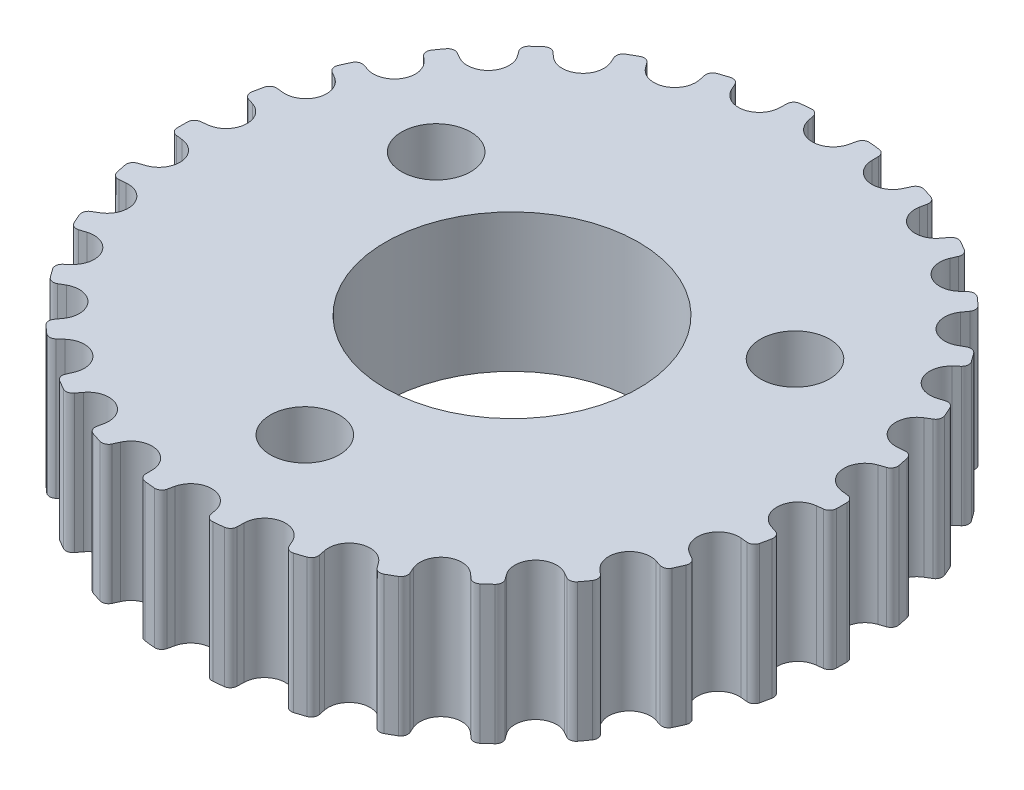
SolidWorks part; units mm, degrees
material "Acrylic (Medium-high impact)"
ref_plane "Front Plane" through (0, 0, 0) normal (0, 0, 1) x (1, 0, 0)
ref_plane "Top Plane" through (0, 0, 0) normal (0, 1, 0) x (1, 0, 0)
ref_plane "Right Plane" through (0, 0, 0) normal (1, 0, 0) x (0, 0, -1)
sketch "Sketch1" plane through (0, 0, 0) normal (0, 1, 0) x (1, 0, 0)
  circle A0 centre (0, 0) radius 14.3239
  dimension "D1" = 28.6479
extrude "Boss-Extrude1" add sketch "Sketch1" along normal blind 6
sketch "Sketch2" plane through (0, 6, 0) normal (0, 1, 0) x (1, 0, 0)
  line L0 (0, 0) -> (0, 14.3239) construction
  line L1 (-0.8883, 13.7564) -> (-0.95, 14.0339)
  line L2 (-2.9781, 14.0109) -> (-2.9781, 14.3239)
  line L3 (-2.9781, 14.3239) -> (2.9781, 14.3239)
  line L4 (0.8883, 13.7564) -> (0.95, 14.0339)
  line L5 (2.9781, 14.0109) -> (2.9781, 14.3239)
  circle A0 centre (0, 0) radius 14.3239 construction
  arc A1 (0.8883, 13.7564) -> (-0.8883, 13.7564) centre (0, 13.9539) cw
  arc A2 (-0.95, 14.0339) -> (-1.2694, 14.2676) centre (-1.2428, 13.9688) ccw
  arc A4 (0.95, 14.0339) -> (1.2694, 14.2676) centre (1.2428, 13.9688) cw
  arc A5 (-1.2694, 14.2676) -> (-2.9781, 14.0109) centre (0, 0) ccw
  arc A6 (1.2694, 14.2676) -> (2.9781, 14.0109) centre (0, 0) cw
  circle A8 centre (0, 0) radius 14.3239 construction
  point P11 (0, 14.3239)
  point P19 (0, 13.0439)
  dimension "D3" = 0.3
  dimension "D5" = 0.91
  dimension "D2" = 0.95
  dimension "D4" = 1.28
  dimension "D6" = 12
extrude "Cut-Extrude1" cut sketch "Sketch2" against normal through all
pattern_circular "CirPattern1" count 30 over 360 about axis through (0, 6, 0) along (0, -1, 0) of "Cut-Extrude1"
sketch "Sketch3" plane through (0, 0, 0) normal (0, -1, 0) x (1, 0, 0)
  circle A0 centre (0, 0) radius 5.5
  dimension "D1" = 11
extrude "Cut-Extrude2" cut sketch "Sketch3" against normal through all
sketch "Sketch4" plane through (0, 0, 0) normal (0, -1, 0) x (1, 0, 0)
  line L0 (0, 0) -> (0, 9) construction
  circle A0 centre (0, 9) radius 1.5
  circle A1 centre (7.7942, -4.5) radius 1.5
  circle A2 centre (-7.7942, -4.5) radius 1.5
  point P14 (0, 0)
  dimension "D1" = 3
  dimension "D2" = 9
  dimension "D3" = 3
extrude "Cut-Extrude3" cut sketch "Sketch4" against normal through all
sketch "Sketch5" plane through (0, 0, 0) normal (0, -1, 0) x (1, 0, 0)
  line L60 (8.7383, -10.682) -> (8.9513, -10.8702)
  line L61 (8.7383, -10.682) -> (8.9513, -10.8702)
  line L62 (9.875, -10.0385) -> (9.7101, -9.807)
  line L63 (9.875, -10.0385) -> (9.7101, -9.807)
  line L64 (12.5987, 6.2896) -> (12.3276, 6.2043)
  line L65 (12.5987, 6.2896) -> (12.3276, 6.2043)
  line L66 (11.5369, 7.5738) -> (11.7463, 7.766)
  line L67 (11.5369, 7.5738) -> (11.7463, 7.766)
  line L68 (-3.638, 13.3126) -> (-3.7561, 13.5712)
  line L69 (-3.638, 13.3126) -> (-3.7561, 13.5712)
  line L70 (-4.9382, 13.1871) -> (-4.8817, 12.9085)
  line L71 (-4.9382, 13.1871) -> (-4.8817, 12.9085)
  line L72 (-11.7463, 7.766) -> (-11.5369, 7.5738)
  line L73 (-11.7463, 7.766) -> (-11.5369, 7.5738)
  line L74 (-12.3276, 6.2043) -> (-12.5987, 6.2896)
  line L75 (-12.3276, 6.2043) -> (-12.5987, 6.2896)
  line L76 (-13.1043, 5.1541) -> (-12.8594, 5.0097)
  line L77 (-13.1043, 5.1541) -> (-12.8594, 5.0097)
  line L78 (-13.3481, 3.5057) -> (-13.6311, 3.5327)
  line L79 (-13.3481, 3.5057) -> (-13.6311, 3.5327)
  line L80 (-13.8895, 2.3169) -> (-13.62, 2.2266)
  line L81 (-13.8895, 2.3169) -> (-13.62, 2.2266)
  line L82 (-13.7853, 0.6538) -> (-14.0677, 0.6215)
  line L83 (-13.7853, 0.6538) -> (-14.0677, 0.6215)
  line L84 (-14.0677, -0.6215) -> (-13.7853, -0.6538)
  line L85 (-14.0677, -0.6215) -> (-13.7853, -0.6538)
  line L86 (-13.62, -2.2266) -> (-13.8895, -2.3169)
  line L87 (-13.62, -2.2266) -> (-13.8895, -2.3169)
  line L88 (-13.6311, -3.5327) -> (-13.3481, -3.5057)
  line L89 (-13.6311, -3.5327) -> (-13.3481, -3.5057)
  line L90 (-12.8594, -5.0097) -> (-13.1043, -5.1541)
  line L91 (-12.8594, -5.0097) -> (-13.1043, -5.1541)
  line L92 (-12.5987, -6.2896) -> (-12.3276, -6.2043)
  line L93 (-12.5987, -6.2896) -> (-12.3276, -6.2043)
  line L94 (-11.5369, -7.5738) -> (-11.7463, -7.766)
  line L95 (-11.5369, -7.5738) -> (-11.7463, -7.766)
  line L96 (-11.0157, -8.7716) -> (-10.7682, -8.6318)
  line L97 (-11.0157, -8.7716) -> (-10.7682, -8.6318)
  line L98 (-9.7101, -9.807) -> (-9.875, -10.0385)
  line L99 (-9.7101, -9.807) -> (-9.875, -10.0385)
  line L100 (-8.9513, -10.8702) -> (-8.7383, -10.682)
  line L101 (-8.9513, -10.8702) -> (-8.7383, -10.682)
  line L102 (-7.4589, -11.6115) -> (-7.5721, -11.8722)
  line L103 (-7.4589, -11.6115) -> (-7.5721, -11.8722)
  line L104 (-6.4956, -12.4937) -> (-6.3264, -12.2653)
  line L105 (-6.4956, -12.4937) -> (-6.3264, -12.2653)
  line L106 (-4.8817, -12.9085) -> (-4.9382, -13.1871)
  line L107 (-4.8817, -12.9085) -> (-4.9382, -13.1871)
  line L108 (-3.7561, -13.5712) -> (-3.638, -13.3126)
  line L109 (-3.7561, -13.5712) -> (-3.638, -13.3126)
  line L110 (-2.0912, -13.6414) -> (-2.0886, -13.9257)
  line L111 (-2.0912, -13.6414) -> (-2.0886, -13.9257)
  line L120 (6.3264, -12.2653) -> (6.4956, -12.4937)
  line L121 (7.5721, -11.8722) -> (7.4589, -11.6115)
  line L124 (10.7682, -8.6318) -> (11.0157, -8.7716)
  line L125 (11.7463, -7.766) -> (11.5369, -7.5738)
  line L126 (12.3276, -6.2043) -> (12.5987, -6.2896)
  line L127 (13.1043, -5.1541) -> (12.8594, -5.0097)
  line L128 (13.3481, -3.5057) -> (13.6311, -3.5327)
  line L129 (13.8895, -2.3169) -> (13.62, -2.2266)
  line L130 (13.7853, -0.6538) -> (14.0677, -0.6215)
  line L131 (14.0677, 0.6215) -> (13.7853, 0.6538)
  line L132 (13.62, 2.2266) -> (13.8895, 2.3169)
  line L133 (13.6311, 3.5327) -> (13.3481, 3.5057)
  line L134 (12.8594, 5.0097) -> (13.1043, 5.1541)
  line L137 (11.0157, 8.7716) -> (10.7682, 8.6318)
  line L138 (9.7101, 9.807) -> (9.875, 10.0385)
  line L139 (8.9513, 10.8702) -> (8.7383, 10.682)
  line L140 (7.4589, 11.6115) -> (7.5721, 11.8722)
  line L141 (6.4956, 12.4937) -> (6.3264, 12.2653)
  line L142 (4.8817, 12.9085) -> (4.9382, 13.1871)
  line L143 (3.7561, 13.5712) -> (3.638, 13.3126)
  line L144 (2.0912, 13.6414) -> (2.0886, 13.9257)
  line L145 (0.8524, 14.0556) -> (0.7907, 13.7781)
  line L146 (-0.7907, 13.7781) -> (-0.8524, 14.0556)
  line L147 (-2.0886, 13.9257) -> (-2.0912, 13.6414)
  line L150 (-6.3264, 12.2653) -> (-6.4956, 12.4937)
  line L151 (-7.5721, 11.8722) -> (-7.4589, 11.6115)
  line L152 (-8.7383, 10.682) -> (-8.9513, 10.8702)
  line L153 (-9.875, 10.0385) -> (-9.7101, 9.807)
  line L154 (-10.7682, 8.6318) -> (-11.0157, 8.7716)
  line L175 (-0.8524, -14.0556) -> (-0.7907, -13.7781)
  line L176 (0.7907, -13.7781) -> (0.8524, -14.0556)
  line L177 (2.0886, -13.9257) -> (2.0912, -13.6414)
  line L178 (3.638, -13.3126) -> (3.7561, -13.5712)
  line L179 (4.9382, -13.1871) -> (4.8817, -12.9085)
  line L180 (6.3264, -12.2653) -> (6.4956, -12.4937)
  line L181 (7.5721, -11.8722) -> (7.4589, -11.6115)
  line L184 (10.7682, -8.6318) -> (11.0157, -8.7716)
  line L185 (11.7463, -7.766) -> (11.5369, -7.5738)
  line L186 (12.3276, -6.2043) -> (12.5987, -6.2896)
  line L187 (13.1043, -5.1541) -> (12.8594, -5.0097)
  line L188 (13.3481, -3.5057) -> (13.6311, -3.5327)
  line L189 (13.8895, -2.3169) -> (13.62, -2.2266)
  line L190 (13.7853, -0.6538) -> (14.0677, -0.6215)
  line L191 (14.0677, 0.6215) -> (13.7853, 0.6538)
  line L192 (13.62, 2.2266) -> (13.8895, 2.3169)
  line L193 (13.6311, 3.5327) -> (13.3481, 3.5057)
  line L194 (12.8594, 5.0097) -> (13.1043, 5.1541)
  line L197 (11.0157, 8.7716) -> (10.7682, 8.6318)
  line L198 (9.7101, 9.807) -> (9.875, 10.0385)
  line L199 (8.9513, 10.8702) -> (8.7383, 10.682)
  line L200 (7.4589, 11.6115) -> (7.5721, 11.8722)
  line L201 (6.4956, 12.4937) -> (6.3264, 12.2653)
  line L202 (4.8817, 12.9085) -> (4.9382, 13.1871)
  line L203 (3.7561, 13.5712) -> (3.638, 13.3126)
  line L204 (2.0912, 13.6414) -> (2.0886, 13.9257)
  line L205 (0.8524, 14.0556) -> (0.7907, 13.7781)
  line L206 (-0.7907, 13.7781) -> (-0.8524, 14.0556)
  line L207 (-2.0886, 13.9257) -> (-2.0912, 13.6414)
  line L210 (-6.3264, 12.2653) -> (-6.4956, 12.4937)
  line L211 (-7.5721, 11.8722) -> (-7.4589, 11.6115)
  line L212 (-8.7383, 10.682) -> (-8.9513, 10.8702)
  line L213 (-9.875, 10.0385) -> (-9.7101, 9.807)
  line L214 (-10.7682, 8.6318) -> (-11.0157, 8.7716)
  line L235 (-0.8524, -14.0556) -> (-0.7907, -13.7781)
  line L236 (0.7907, -13.7781) -> (0.8524, -14.0556)
  line L237 (2.0886, -13.9257) -> (2.0912, -13.6414)
  line L238 (3.638, -13.3126) -> (3.7561, -13.5712)
  line L239 (4.9382, -13.1871) -> (4.8817, -12.9085)
  arc A76 (8.9513, -10.8702) -> (9.479, -10.8719) centre (9.2161, -10.5704) ccw
  arc A77 (8.9513, -10.8702) -> (9.479, -10.8719) centre (9.2161, -10.5704) ccw
  arc A78 (9.479, -10.8719) -> (9.8216, -10.5635) centre (0, 0) ccw
  arc A79 (9.479, -10.8719) -> (9.8216, -10.5635) centre (0, 0) ccw
  arc A80 (9.8216, -10.5635) -> (9.875, -10.0385) centre (9.5492, -10.2705) ccw
  arc A81 (9.8216, -10.5635) -> (9.875, -10.0385) centre (9.5492, -10.2705) ccw
  circle A120 centre (0, 0) radius 13.0439
  arc A121 (-0.8883, 13.7564) -> (0.8883, 13.7564) centre (0, 13.9539) ccw construction
  arc A128 (11.5369, 7.5738) -> (12.3276, 6.2043) centre (12.0845, 6.977) ccw
  arc A129 (11.5369, 7.5738) -> (12.3276, 6.2043) centre (12.0845, 6.977) ccw
  arc A130 (-3.7561, 13.5712) -> (-4.2375, 13.7875) centre (-4.12, 13.4051) ccw
  arc A131 (-3.7561, 13.5712) -> (-4.2375, 13.7875) centre (-4.12, 13.4051) ccw
  arc A132 (-4.2375, 13.7875) -> (-4.6759, 13.645) centre (0, 0) ccw
  arc A133 (-4.2375, 13.7875) -> (-4.6759, 13.645) centre (0, 0) ccw
  arc A134 (-4.6759, 13.645) -> (-4.9382, 13.1871) centre (-4.5462, 13.2666) ccw
  arc A135 (-4.6759, 13.645) -> (-4.9382, 13.1871) centre (-4.5462, 13.2666) ccw
  arc A136 (-11.8032, 8.2906) -> (-11.7463, 7.766) centre (-11.4759, 8.0607) ccw
  arc A137 (-11.8032, 8.2906) -> (-11.7463, 7.766) centre (-11.4759, 8.0607) ccw
  arc A138 (-12.3276, 6.2043) -> (-11.5369, 7.5738) centre (-12.0845, 6.977) ccw
  arc A139 (-12.3276, 6.2043) -> (-11.5369, 7.5738) centre (-12.0845, 6.977) ccw
  arc A140 (-12.5987, 6.2896) -> (-13.0815, 6.0766) centre (-12.7187, 5.908) ccw
  arc A141 (-12.5987, 6.2896) -> (-13.0815, 6.0766) centre (-12.7187, 5.908) ccw
  arc A142 (-13.0815, 6.0766) -> (-13.269, 5.6554) centre (0, 0) ccw
  arc A143 (-13.0815, 6.0766) -> (-13.269, 5.6554) centre (0, 0) ccw
  arc A144 (-13.269, 5.6554) -> (-13.1043, 5.1541) centre (-12.901, 5.4986) ccw
  arc A145 (-13.269, 5.6554) -> (-13.1043, 5.1541) centre (-12.901, 5.4986) ccw
  arc A146 (-13.3481, 3.5057) -> (-12.8594, 5.0097) centre (-13.271, 4.312) ccw
  arc A147 (-13.3481, 3.5057) -> (-12.8594, 5.0097) centre (-13.271, 4.312) ccw
  arc A148 (-13.6311, 3.5327) -> (-14.059, 3.224) centre (-13.6691, 3.1346) ccw
  arc A149 (-13.6311, 3.5327) -> (-14.059, 3.224) centre (-13.6691, 3.1346) ccw
  arc A150 (-14.059, 3.224) -> (-14.1549, 2.7731) centre (0, 0) ccw
  arc A151 (-14.059, 3.224) -> (-14.1549, 2.7731) centre (0, 0) ccw
  arc A152 (-14.1549, 2.7731) -> (-13.8895, 2.3169) centre (-13.7623, 2.6962) ccw
  arc A153 (-14.1549, 2.7731) -> (-13.8895, 2.3169) centre (-13.7623, 2.6962) ccw
  arc A154 (-13.7853, 0.6538) -> (-13.62, 2.2266) centre (-13.8775, 1.4586) ccw
  arc A155 (-13.7853, 0.6538) -> (-13.62, 2.2266) centre (-13.8775, 1.4586) ccw
  arc A156 (-14.0677, 0.6215) -> (-14.4221, 0.2305) centre (-14.0222, 0.2241) ccw
  arc A157 (-14.0677, 0.6215) -> (-14.4221, 0.2305) centre (-14.0222, 0.2241) ccw
  arc A158 (-14.4221, 0.2305) -> (-14.4221, -0.2305) centre (0, 0) ccw
  arc A159 (-14.4221, 0.2305) -> (-14.4221, -0.2305) centre (0, 0) ccw
  arc A160 (-14.4221, -0.2305) -> (-14.0677, -0.6215) centre (-14.0222, -0.2241) ccw
  arc A161 (-14.4221, -0.2305) -> (-14.0677, -0.6215) centre (-14.0222, -0.2241) ccw
  arc A162 (-13.62, -2.2266) -> (-13.7853, -0.6538) centre (-13.8775, -1.4586) ccw
  arc A163 (-13.62, -2.2266) -> (-13.7853, -0.6538) centre (-13.8775, -1.4586) ccw
  arc A164 (-13.8895, -2.3169) -> (-14.1549, -2.7731) centre (-13.7623, -2.6962) ccw
  arc A165 (-13.8895, -2.3169) -> (-14.1549, -2.7731) centre (-13.7623, -2.6962) ccw
  arc A166 (-14.1549, -2.7731) -> (-14.059, -3.224) centre (0, 0) ccw
  arc A167 (-14.1549, -2.7731) -> (-14.059, -3.224) centre (0, 0) ccw
  arc A168 (-14.059, -3.224) -> (-13.6311, -3.5327) centre (-13.6691, -3.1346) ccw
  arc A169 (-14.059, -3.224) -> (-13.6311, -3.5327) centre (-13.6691, -3.1346) ccw
  arc A170 (-12.8594, -5.0097) -> (-13.3481, -3.5057) centre (-13.271, -4.312) ccw
  arc A171 (-12.8594, -5.0097) -> (-13.3481, -3.5057) centre (-13.271, -4.312) ccw
  arc A172 (-13.1043, -5.1541) -> (-13.269, -5.6554) centre (-12.901, -5.4986) ccw
  arc A173 (-13.1043, -5.1541) -> (-13.269, -5.6554) centre (-12.901, -5.4986) ccw
  arc A174 (-13.269, -5.6554) -> (-13.0815, -6.0766) centre (0, 0) ccw
  arc A175 (-13.269, -5.6554) -> (-13.0815, -6.0766) centre (0, 0) ccw
  arc A176 (-13.0815, -6.0766) -> (-12.5987, -6.2896) centre (-12.7187, -5.908) ccw
  arc A177 (-13.0815, -6.0766) -> (-12.5987, -6.2896) centre (-12.7187, -5.908) ccw
  arc A178 (-11.5369, -7.5738) -> (-12.3276, -6.2043) centre (-12.0845, -6.977) ccw
  arc A179 (-11.5369, -7.5738) -> (-12.3276, -6.2043) centre (-12.0845, -6.977) ccw
  arc A180 (-11.7463, -7.766) -> (-11.8032, -8.2906) centre (-11.4759, -8.0607) ccw
  arc A181 (-11.7463, -7.766) -> (-11.8032, -8.2906) centre (-11.4759, -8.0607) ccw
  arc A182 (-11.8032, -8.2906) -> (-11.5323, -8.6636) centre (0, 0) ccw
  arc A183 (-11.8032, -8.2906) -> (-11.5323, -8.6636) centre (0, 0) ccw
  arc A184 (-11.5323, -8.6636) -> (-11.0157, -8.7716) centre (-11.2124, -8.4233) ccw
  arc A185 (-11.5323, -8.6636) -> (-11.0157, -8.7716) centre (-11.2124, -8.4233) ccw
  arc A186 (-9.7101, -9.807) -> (-10.7682, -8.6318) centre (-10.3698, -9.337) ccw
  arc A187 (-9.7101, -9.807) -> (-10.7682, -8.6318) centre (-10.3698, -9.337) ccw
  arc A188 (-9.875, -10.0385) -> (-9.8216, -10.5635) centre (-9.5492, -10.2705) ccw
  arc A189 (-9.875, -10.0385) -> (-9.8216, -10.5635) centre (-9.5492, -10.2705) ccw
  arc A190 (-9.8216, -10.5635) -> (-9.479, -10.8719) centre (0, 0) ccw
  arc A191 (-9.8216, -10.5635) -> (-9.479, -10.8719) centre (0, 0) ccw
  arc A192 (-9.479, -10.8719) -> (-8.9513, -10.8702) centre (-9.2161, -10.5704) ccw
  arc A193 (-9.479, -10.8719) -> (-8.9513, -10.8702) centre (-9.2161, -10.5704) ccw
  arc A194 (-7.4589, -11.6115) -> (-8.7383, -10.682) centre (-8.2019, -11.289) ccw
  arc A195 (-7.4589, -11.6115) -> (-8.7383, -10.682) centre (-8.2019, -11.289) ccw
  arc A196 (-7.5721, -11.8722) -> (-7.4107, -12.3747) centre (-7.2051, -12.0315) ccw
  arc A197 (-7.5721, -11.8722) -> (-7.4107, -12.3747) centre (-7.2051, -12.0315) ccw
  arc A198 (-7.4107, -12.3747) -> (-7.0114, -12.6052) centre (0, 0) ccw
  arc A199 (-7.4107, -12.3747) -> (-7.0114, -12.6052) centre (0, 0) ccw
  arc A200 (-7.0114, -12.6052) -> (-6.4956, -12.4937) centre (-6.817, -12.2556) ccw
  arc A201 (-7.0114, -12.6052) -> (-6.4956, -12.4937) centre (-6.817, -12.2556) ccw
  arc A202 (-4.8817, -12.9085) -> (-6.3264, -12.2653) centre (-5.6756, -12.7476) ccw
  arc A203 (-4.8817, -12.9085) -> (-6.3264, -12.2653) centre (-5.6756, -12.7476) ccw
  arc A204 (-4.9382, -13.1871) -> (-4.6759, -13.645) centre (-4.5462, -13.2666) ccw
  arc A205 (-4.9382, -13.1871) -> (-4.6759, -13.645) centre (-4.5462, -13.2666) ccw
  arc A206 (-4.6759, -13.645) -> (-4.2375, -13.7875) centre (0, 0) ccw
  arc A207 (-4.6759, -13.645) -> (-4.2375, -13.7875) centre (0, 0) ccw
  arc A208 (-4.2375, -13.7875) -> (-3.7561, -13.5712) centre (-4.12, -13.4051) ccw
  arc A209 (-4.2375, -13.7875) -> (-3.7561, -13.5712) centre (-4.12, -13.4051) ccw
  arc A210 (-2.0912, -13.6414) -> (-3.638, -13.3126) centre (-2.9012, -13.649) ccw
  arc A211 (-2.0912, -13.6414) -> (-3.638, -13.3126) centre (-2.9012, -13.649) ccw
  arc A212 (-2.0886, -13.9257) -> (-1.7367, -14.319) centre (-1.6886, -13.9219) ccw
  arc A213 (-2.0886, -13.9257) -> (-1.7367, -14.319) centre (-1.6886, -13.9219) ccw
  arc A214 (-1.7367, -14.319) -> (-1.2783, -14.3672) centre (0, 0) ccw
  arc A215 (-1.7367, -14.319) -> (-1.2783, -14.3672) centre (0, 0) ccw
  arc A240 (6.4956, -12.4937) -> (7.0114, -12.6052) centre (6.817, -12.2556) ccw
  arc A241 (7.0114, -12.6052) -> (7.4107, -12.3747) centre (0, 0) ccw
  arc A242 (7.4107, -12.3747) -> (7.5721, -11.8722) centre (7.2051, -12.0315) ccw
  arc A243 (8.7383, -10.682) -> (7.4589, -11.6115) centre (8.2019, -11.289) ccw
  arc A247 (10.7682, -8.6318) -> (9.7101, -9.807) centre (10.3698, -9.337) ccw
  arc A248 (11.0157, -8.7716) -> (11.5323, -8.6636) centre (11.2124, -8.4233) ccw
  arc A249 (11.5323, -8.6636) -> (11.8032, -8.2906) centre (0, 0) ccw
  arc A250 (11.8032, -8.2906) -> (11.7463, -7.766) centre (11.4759, -8.0607) ccw
  arc A251 (12.3276, -6.2043) -> (11.5369, -7.5738) centre (12.0845, -6.977) ccw
  arc A252 (12.5987, -6.2896) -> (13.0815, -6.0766) centre (12.7187, -5.908) ccw
  arc A253 (13.0815, -6.0766) -> (13.269, -5.6554) centre (0, 0) ccw
  arc A254 (13.269, -5.6554) -> (13.1043, -5.1541) centre (12.901, -5.4986) ccw
  arc A255 (13.3481, -3.5057) -> (12.8594, -5.0097) centre (13.271, -4.312) ccw
  arc A256 (13.6311, -3.5327) -> (14.059, -3.224) centre (13.6691, -3.1346) ccw
  arc A257 (14.059, -3.224) -> (14.1549, -2.7731) centre (0, 0) ccw
  arc A258 (14.1549, -2.7731) -> (13.8895, -2.3169) centre (13.7623, -2.6962) ccw
  arc A259 (13.7853, -0.6538) -> (13.62, -2.2266) centre (13.8775, -1.4586) ccw
  arc A260 (14.0677, -0.6215) -> (14.4221, -0.2305) centre (14.0222, -0.2241) ccw
  arc A261 (14.4221, -0.2305) -> (14.4221, 0.2305) centre (0, 0) ccw
  arc A262 (14.4221, 0.2305) -> (14.0677, 0.6215) centre (14.0222, 0.2241) ccw
  arc A263 (13.62, 2.2266) -> (13.7853, 0.6538) centre (13.8775, 1.4586) ccw
  arc A264 (13.8895, 2.3169) -> (14.1549, 2.7731) centre (13.7623, 2.6962) ccw
  arc A265 (14.1549, 2.7731) -> (14.059, 3.224) centre (0, 0) ccw
  arc A266 (14.059, 3.224) -> (13.6311, 3.5327) centre (13.6691, 3.1346) ccw
  arc A267 (12.8594, 5.0097) -> (13.3481, 3.5057) centre (13.271, 4.312) ccw
  arc A268 (13.1043, 5.1541) -> (13.269, 5.6554) centre (12.901, 5.4986) ccw
  arc A269 (13.269, 5.6554) -> (13.0815, 6.0766) centre (0, 0) ccw
  arc A270 (13.0815, 6.0766) -> (12.5987, 6.2896) centre (12.7187, 5.908) ccw
  arc A272 (11.7463, 7.766) -> (11.8032, 8.2906) centre (11.4759, 8.0607) ccw
  arc A273 (11.8032, 8.2906) -> (11.5323, 8.6636) centre (0, 0) ccw
  arc A274 (11.5323, 8.6636) -> (11.0157, 8.7716) centre (11.2124, 8.4233) ccw
  arc A275 (9.7101, 9.807) -> (10.7682, 8.6318) centre (10.3698, 9.337) ccw
  arc A276 (9.875, 10.0385) -> (9.8216, 10.5635) centre (9.5492, 10.2705) ccw
  arc A277 (9.8216, 10.5635) -> (9.479, 10.8719) centre (0, 0) ccw
  arc A278 (9.479, 10.8719) -> (8.9513, 10.8702) centre (9.2161, 10.5704) ccw
  arc A279 (7.4589, 11.6115) -> (8.7383, 10.682) centre (8.2019, 11.289) ccw
  arc A280 (7.5721, 11.8722) -> (7.4107, 12.3747) centre (7.2051, 12.0315) ccw
  arc A281 (7.4107, 12.3747) -> (7.0114, 12.6052) centre (0, 0) ccw
  arc A282 (7.0114, 12.6052) -> (6.4956, 12.4937) centre (6.817, 12.2556) ccw
  arc A283 (4.8817, 12.9085) -> (6.3264, 12.2653) centre (5.6756, 12.7476) ccw
  arc A284 (4.9382, 13.1871) -> (4.6759, 13.645) centre (4.5462, 13.2666) ccw
  arc A285 (4.6759, 13.645) -> (4.2375, 13.7875) centre (0, 0) ccw
  arc A286 (4.2375, 13.7875) -> (3.7561, 13.5712) centre (4.12, 13.4051) ccw
  arc A287 (2.0912, 13.6414) -> (3.638, 13.3126) centre (2.9012, 13.649) ccw
  arc A288 (2.0886, 13.9257) -> (1.7367, 14.319) centre (1.6886, 13.9219) ccw
  arc A289 (1.7367, 14.319) -> (1.2783, 14.3672) centre (0, 0) ccw
  arc A290 (1.2783, 14.3672) -> (0.8524, 14.0556) centre (1.2428, 13.9688) ccw
  arc A291 (-0.7907, 13.7781) -> (0.7907, 13.7781) centre (0, 13.9539) ccw
  arc A292 (-0.8524, 14.0556) -> (-1.2783, 14.3672) centre (-1.2428, 13.9688) ccw
  arc A293 (-1.2783, 14.3672) -> (-1.7367, 14.319) centre (0, 0) ccw
  arc A294 (-1.7367, 14.319) -> (-2.0886, 13.9257) centre (-1.6886, 13.9219) ccw
  arc A295 (-3.638, 13.3126) -> (-2.0912, 13.6414) centre (-2.9012, 13.649) ccw
  arc A299 (-6.3264, 12.2653) -> (-4.8817, 12.9085) centre (-5.6756, 12.7476) ccw
  arc A300 (-6.4956, 12.4937) -> (-7.0114, 12.6052) centre (-6.817, 12.2556) ccw
  arc A301 (-7.0114, 12.6052) -> (-7.4107, 12.3747) centre (0, 0) ccw
  arc A302 (-7.4107, 12.3747) -> (-7.5721, 11.8722) centre (-7.2051, 12.0315) ccw
  arc A303 (-8.7383, 10.682) -> (-7.4589, 11.6115) centre (-8.2019, 11.289) ccw
  arc A304 (-8.9513, 10.8702) -> (-9.479, 10.8719) centre (-9.2161, 10.5704) ccw
  arc A305 (-9.479, 10.8719) -> (-9.8216, 10.5635) centre (0, 0) ccw
  arc A306 (-9.8216, 10.5635) -> (-9.875, 10.0385) centre (-9.5492, 10.2705) ccw
  arc A307 (-10.7682, 8.6318) -> (-9.7101, 9.807) centre (-10.3698, 9.337) ccw
  arc A308 (-11.0157, 8.7716) -> (-11.5323, 8.6636) centre (-11.2124, 8.4233) ccw
  arc A309 (-11.5323, 8.6636) -> (-11.8032, 8.2906) centre (0, 0) ccw
  arc A350 (-1.2783, -14.3672) -> (-0.8524, -14.0556) centre (-1.2428, -13.9688) ccw
  arc A351 (0.7907, -13.7781) -> (-0.7907, -13.7781) centre (0, -13.9539) ccw
  arc A352 (0.8524, -14.0556) -> (1.2783, -14.3672) centre (1.2428, -13.9688) ccw
  arc A353 (1.2783, -14.3672) -> (1.7367, -14.319) centre (0, 0) ccw
  arc A354 (1.7367, -14.319) -> (2.0886, -13.9257) centre (1.6886, -13.9219) ccw
  arc A355 (3.638, -13.3126) -> (2.0912, -13.6414) centre (2.9012, -13.649) ccw
  arc A356 (3.7561, -13.5712) -> (4.2375, -13.7875) centre (4.12, -13.4051) ccw
  arc A357 (4.2375, -13.7875) -> (4.6759, -13.645) centre (0, 0) ccw
  arc A358 (4.6759, -13.645) -> (4.9382, -13.1871) centre (4.5462, -13.2666) ccw
  arc A359 (6.3264, -12.2653) -> (4.8817, -12.9085) centre (5.6756, -12.7476) ccw
  arc A360 (6.4956, -12.4937) -> (7.0114, -12.6052) centre (6.817, -12.2556) ccw
  arc A361 (7.0114, -12.6052) -> (7.4107, -12.3747) centre (0, 0) ccw
  arc A362 (7.4107, -12.3747) -> (7.5721, -11.8722) centre (7.2051, -12.0315) ccw
  arc A363 (8.7383, -10.682) -> (7.4589, -11.6115) centre (8.2019, -11.289) ccw
  arc A367 (10.7682, -8.6318) -> (9.7101, -9.807) centre (10.3698, -9.337) ccw
  arc A368 (11.0157, -8.7716) -> (11.5323, -8.6636) centre (11.2124, -8.4233) ccw
  arc A369 (11.5323, -8.6636) -> (11.8032, -8.2906) centre (0, 0) ccw
  arc A370 (11.8032, -8.2906) -> (11.7463, -7.766) centre (11.4759, -8.0607) ccw
  arc A371 (12.3276, -6.2043) -> (11.5369, -7.5738) centre (12.0845, -6.977) ccw
  arc A372 (12.5987, -6.2896) -> (13.0815, -6.0766) centre (12.7187, -5.908) ccw
  arc A373 (13.0815, -6.0766) -> (13.269, -5.6554) centre (0, 0) ccw
  arc A374 (13.269, -5.6554) -> (13.1043, -5.1541) centre (12.901, -5.4986) ccw
  arc A375 (13.3481, -3.5057) -> (12.8594, -5.0097) centre (13.271, -4.312) ccw
  arc A376 (13.6311, -3.5327) -> (14.059, -3.224) centre (13.6691, -3.1346) ccw
  arc A377 (14.059, -3.224) -> (14.1549, -2.7731) centre (0, 0) ccw
  arc A378 (14.1549, -2.7731) -> (13.8895, -2.3169) centre (13.7623, -2.6962) ccw
  arc A379 (13.7853, -0.6538) -> (13.62, -2.2266) centre (13.8775, -1.4586) ccw
  arc A380 (14.0677, -0.6215) -> (14.4221, -0.2305) centre (14.0222, -0.2241) ccw
  arc A381 (14.4221, -0.2305) -> (14.4221, 0.2305) centre (0, 0) ccw
  arc A382 (14.4221, 0.2305) -> (14.0677, 0.6215) centre (14.0222, 0.2241) ccw
  arc A383 (13.62, 2.2266) -> (13.7853, 0.6538) centre (13.8775, 1.4586) ccw
  arc A384 (13.8895, 2.3169) -> (14.1549, 2.7731) centre (13.7623, 2.6962) ccw
  arc A385 (14.1549, 2.7731) -> (14.059, 3.224) centre (0, 0) ccw
  arc A386 (14.059, 3.224) -> (13.6311, 3.5327) centre (13.6691, 3.1346) ccw
  arc A387 (12.8594, 5.0097) -> (13.3481, 3.5057) centre (13.271, 4.312) ccw
  arc A388 (13.1043, 5.1541) -> (13.269, 5.6554) centre (12.901, 5.4986) ccw
  arc A389 (13.269, 5.6554) -> (13.0815, 6.0766) centre (0, 0) ccw
  arc A390 (13.0815, 6.0766) -> (12.5987, 6.2896) centre (12.7187, 5.908) ccw
  arc A392 (11.7463, 7.766) -> (11.8032, 8.2906) centre (11.4759, 8.0607) ccw
  arc A393 (11.8032, 8.2906) -> (11.5323, 8.6636) centre (0, 0) ccw
  arc A394 (11.5323, 8.6636) -> (11.0157, 8.7716) centre (11.2124, 8.4233) ccw
  arc A395 (9.7101, 9.807) -> (10.7682, 8.6318) centre (10.3698, 9.337) ccw
  arc A396 (9.875, 10.0385) -> (9.8216, 10.5635) centre (9.5492, 10.2705) ccw
  arc A397 (9.8216, 10.5635) -> (9.479, 10.8719) centre (0, 0) ccw
  arc A398 (9.479, 10.8719) -> (8.9513, 10.8702) centre (9.2161, 10.5704) ccw
  arc A399 (7.4589, 11.6115) -> (8.7383, 10.682) centre (8.2019, 11.289) ccw
  arc A400 (7.5721, 11.8722) -> (7.4107, 12.3747) centre (7.2051, 12.0315) ccw
  arc A401 (7.4107, 12.3747) -> (7.0114, 12.6052) centre (0, 0) ccw
  arc A402 (7.0114, 12.6052) -> (6.4956, 12.4937) centre (6.817, 12.2556) ccw
  arc A403 (4.8817, 12.9085) -> (6.3264, 12.2653) centre (5.6756, 12.7476) ccw
  arc A404 (4.9382, 13.1871) -> (4.6759, 13.645) centre (4.5462, 13.2666) ccw
  arc A405 (4.6759, 13.645) -> (4.2375, 13.7875) centre (0, 0) ccw
  arc A406 (4.2375, 13.7875) -> (3.7561, 13.5712) centre (4.12, 13.4051) ccw
  arc A407 (2.0912, 13.6414) -> (3.638, 13.3126) centre (2.9012, 13.649) ccw
  arc A408 (2.0886, 13.9257) -> (1.7367, 14.319) centre (1.6886, 13.9219) ccw
  arc A409 (1.7367, 14.319) -> (1.2783, 14.3672) centre (0, 0) ccw
  arc A410 (1.2783, 14.3672) -> (0.8524, 14.0556) centre (1.2428, 13.9688) ccw
  arc A411 (-0.7907, 13.7781) -> (0.7907, 13.7781) centre (0, 13.9539) ccw
  arc A412 (-0.8524, 14.0556) -> (-1.2783, 14.3672) centre (-1.2428, 13.9688) ccw
  arc A413 (-1.2783, 14.3672) -> (-1.7367, 14.319) centre (0, 0) ccw
  arc A414 (-1.7367, 14.319) -> (-2.0886, 13.9257) centre (-1.6886, 13.9219) ccw
  arc A415 (-3.638, 13.3126) -> (-2.0912, 13.6414) centre (-2.9012, 13.649) ccw
  arc A419 (-6.3264, 12.2653) -> (-4.8817, 12.9085) centre (-5.6756, 12.7476) ccw
  arc A420 (-6.4956, 12.4937) -> (-7.0114, 12.6052) centre (-6.817, 12.2556) ccw
  arc A421 (-7.0114, 12.6052) -> (-7.4107, 12.3747) centre (0, 0) ccw
  arc A422 (-7.4107, 12.3747) -> (-7.5721, 11.8722) centre (-7.2051, 12.0315) ccw
  arc A423 (-8.7383, 10.682) -> (-7.4589, 11.6115) centre (-8.2019, 11.289) ccw
  arc A424 (-8.9513, 10.8702) -> (-9.479, 10.8719) centre (-9.2161, 10.5704) ccw
  arc A425 (-9.479, 10.8719) -> (-9.8216, 10.5635) centre (0, 0) ccw
  arc A426 (-9.8216, 10.5635) -> (-9.875, 10.0385) centre (-9.5492, 10.2705) ccw
  arc A427 (-10.7682, 8.6318) -> (-9.7101, 9.807) centre (-10.3698, 9.337) ccw
  arc A428 (-11.0157, 8.7716) -> (-11.5323, 8.6636) centre (-11.2124, 8.4233) ccw
  arc A429 (-11.5323, 8.6636) -> (-11.8032, 8.2906) centre (0, 0) ccw
  arc A470 (-1.2783, -14.3672) -> (-0.8524, -14.0556) centre (-1.2428, -13.9688) ccw
  arc A471 (0.7907, -13.7781) -> (-0.7907, -13.7781) centre (0, -13.9539) ccw
  arc A472 (0.8524, -14.0556) -> (1.2783, -14.3672) centre (1.2428, -13.9688) ccw
  arc A473 (1.2783, -14.3672) -> (1.7367, -14.319) centre (0, 0) ccw
  arc A474 (1.7367, -14.319) -> (2.0886, -13.9257) centre (1.6886, -13.9219) ccw
  arc A475 (3.638, -13.3126) -> (2.0912, -13.6414) centre (2.9012, -13.649) ccw
  arc A476 (3.7561, -13.5712) -> (4.2375, -13.7875) centre (4.12, -13.4051) ccw
  arc A477 (4.2375, -13.7875) -> (4.6759, -13.645) centre (0, 0) ccw
  arc A478 (4.6759, -13.645) -> (4.9382, -13.1871) centre (4.5462, -13.2666) ccw
  arc A479 (6.3264, -12.2653) -> (4.8817, -12.9085) centre (5.6756, -12.7476) ccw
  dimension "D1" = 0.1
extrude "Boss-Extrude2" [suppressed] add sketch "Sketch5" against normal up to surface (5.8 mm away) up to face at (7.7942, 6, -6)
equation "\"smallPulleyTeeth\"= 30"
equation "\"largePulleyTeeth\"= 30"
equation "\"eighthThick\"= 3.0mm"
equation "\"D1@Sketch1\"=3*\"largePulleyTeeth\"/pi"
equation "\"D1@Boss-Extrude1\" = \"eighthThick\" * 2"
equation "\"D6@Sketch2\"=360/\"largePulleyTeeth\""
equation "\"quarterThick\"=6.0mm"
equation "\"D1@CirPattern1\"=\"largePulleyTeeth\""
equation "\"sixteenthThick\"= 1.7mm"
equation "\"OD\"= 145mm"
equation "\"puckAngle\"= 60.5deg"
equation "\"puckDiam\"= 76.5mm"
equation "\"axlePress\"= 5.9mm"
equation "\"press\"= 0.2mm"
equation "\"wheelClear\"= 0.3mm"
equation "\"10-32clear\"= 4.8mm"
equation "\"D1@Sketch4\"=\"4-40clear\""
equation "\"6-32clear\"= 3.3mm"
equation "\"8-32clear\"= 4.0mm"
equation "\"4-40clear\"= 3.0mm"
equation "\"wheelHeight\"= 22mm"
equation "\"wheelWell\"= 65mm"
